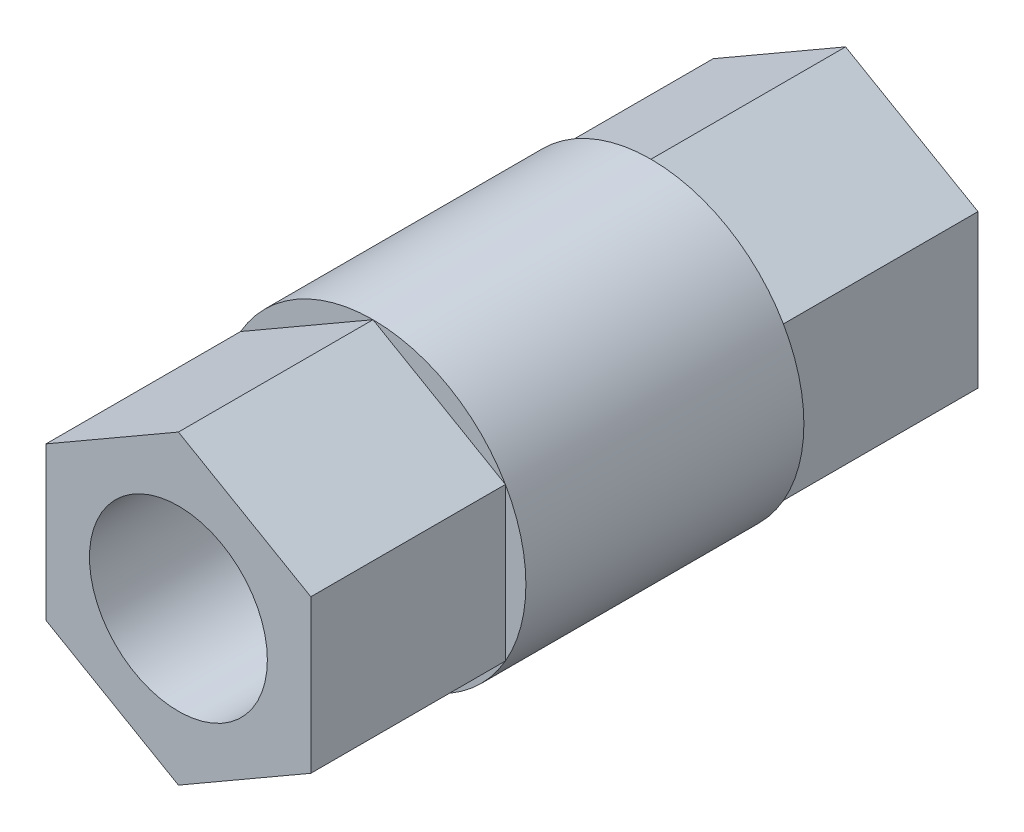
SolidWorks part; units mm, degrees
ref_plane "Front Plane" through (0, 0, 0) normal (0, 0, 1) x (1, 0, 0)
ref_plane "Top Plane" through (0, 0, 0) normal (0, 1, 0) x (1, 0, 0)
ref_plane "Right Plane" through (0, 0, 0) normal (1, 0, 0) x (0, 0, -1)
sketch "Sketch1" plane through (0, 0, 0) normal (0, 0, 1) x (1, 0, 0)
  line L1 (0, -11) -> (9.5263, -5.5)
  line L2 (9.5263, -5.5) -> (9.5263, 5.5)
  line L3 (9.5263, 5.5) -> (0, 11)
  line L4 (0, 11) -> (-9.5263, 5.5)
  line L5 (-9.5263, 5.5) -> (-9.5263, -5.5)
  line L6 (-9.5263, -5.5) -> (0, -11)
  circle A0 centre (0, 0) radius 11
  circle A1 centre (0, 0) radius 9.5263 construction
  circle A2 centre (0, 0) radius 6.4
  dimension "D1" = 22
  dimension "D2" = 12.8
extrude "Boss-Extrude1" add sketch "Sketch1" along normal mid plane 20 contours L4 A0 | L5 A0 | L5 L6 L1 L2 L3 L4 | L3 A0 | L2 A0 | L1 A0 | L6 A0 region at (-4.6176, -7.998, 0) region at (-5.0596, -8.7636, 0) region at (5.0596, -8.7636, 0) region at (10.1193, 0, 0) region at (-10.1193, 0, 0) region at (5.0596, 8.7636, 0) region at (-5.0596, 8.7636, 0)
extrude "Boss-Extrude2" add sketch "Sketch1<3>" along normal mid plane 48 contours L5 L6 L1 L2 L3 L4 A2 region at (-4.6176, -7.998, 0)
sketch "Sketch1<3>" plane through (0, 0, 0) normal (0, 0, 1) x (1, 0, 0) same geometry as "Sketch1"
